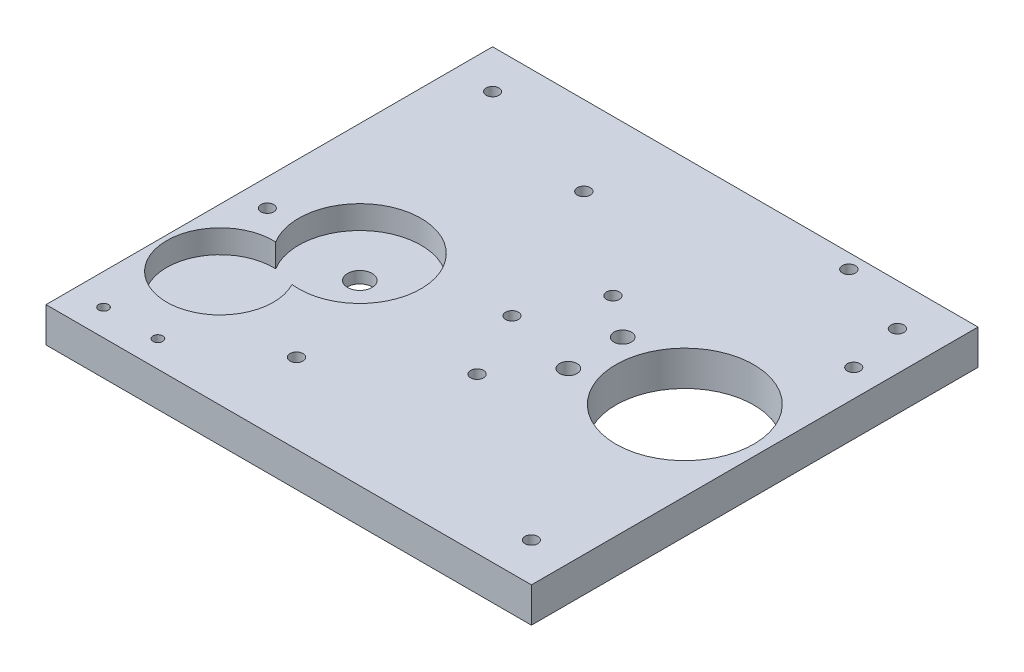
SolidWorks part; units mm, degrees
ref_plane "Front" through (0, 0, 0) normal (0, 0, 1) x (1, 0, 0)
ref_plane "Top" through (0, 0, 0) normal (0, 1, 0) x (1, 0, 0)
ref_plane "Right" through (0, 0, 0) normal (1, 0, 0) x (0, 0, -1)
sketch "Sketch1" plane through (0, 0, 0) normal (0, 1, 0) x (1, 0, 0)
  line L1 (0, 0) -> (125, 0)
  line L2 (0, 0) -> (0, 115)
  line L3 (0, 115) -> (125, 115)
  line L4 (125, 0) -> (125, 115)
  dimension "D1" = 125
  dimension "D2" = 115
extrude "Top_Base" add sketch "Sketch1" along normal blind 9
sketch "Fingers_Position" plane through (0, 9, 0) normal (0, 1, 0) x (1, 0, 0)
  line L0 (74.5, 94.5) -> (39.5, 94.5) construction
  line L1 (74.5, 78.5) -> (19.5, 78.5) construction
  line L2 (74.5, 78.5) -> (74.5, 110.5) construction
  line L3 (74.5, 110.5) -> (19.5, 110.5) construction
  line L4 (19.5, 78.5) -> (19.5, 110.5) construction
  line L5 (74.5, 9.5) -> (19.5, 9.5) construction
  line L6 (74.5, 9.5) -> (74.5, 41.5) construction
  line L7 (74.5, 41.5) -> (19.5, 41.5) construction
  line L8 (19.5, 9.5) -> (19.5, 41.5) construction
  line L10 (39.5, 25.5) -> (74.5, 25.5) construction
  line L11 (125, 115) -> (0, 115) construction
  line L12 (0, 115) -> (0, 0) construction
  dimension "D1" = 55
  dimension "D2" = 32
  dimension "D3" = 69
  dimension "D4" = 4.5
  dimension "D5" = 19.5
  dimension "D6" = 20
sketch "Intermediate_Gear_Position" plane through (0, 9, 0) normal (0, 1, 0) x (1, 0, 0)
  line L0 (0, 51.7935) -> (29.0154, 51.7935) construction
  line L1 (0, 115) -> (0, 0) construction
  line L2 (29.0154, 51.7935) -> (29.0154, 115) construction
  line L3 (125, 115) -> (0, 115) construction
  line L4 (29.0154, 51.7935) -> (29.0154, 0) construction
  line L5 (0, 0) -> (125, 0) construction
  circle A0 centre (29.0154, 51.7935) radius 15.5 construction
  circle A1 centre (29.0154, 51.7935) radius 13.5625
  circle A2 centre (29.0154, 51.7935) radius 13.8125 construction
  dimension "D3" = 31
  dimension "D4" = 27.125
  dimension "D5" = 27.625
  dimension "D1" = 29.0154
  dimension "D2" = 51.7935
sketch "Drive_Gear_Position" plane through (0, 9, 0) normal (0, 1, 0) x (1, 0, 0)
  line L0 (3, 20.8203) -> (27, 20.8203) construction
  line L1 (3, 38.8203) -> (27, 38.8203)
  line L2 (3, 38.8203) -> (3, 2.8203)
  line L3 (3, 2.8203) -> (27, 2.8203)
  line L4 (27, 38.8203) -> (27, 2.8203)
  line L5 (15, 38.8203) -> (15, 2.8203) construction
  line L6 (95.5, 103) -> (95.5, 48) construction
  line L7 (79.5, 103) -> (111.5, 103) construction
  line L8 (79.5, 103) -> (79.5, 48) construction
  line L9 (79.5, 48) -> (111.5, 48) construction
  line L10 (111.5, 103) -> (111.5, 48) construction
  line L11 (77.5, 72) -> (113.5, 72) construction
  line L12 (77.5, 72) -> (77.5, 48) construction
  line L13 (77.5, 48) -> (113.5, 48) construction
  line L14 (113.5, 72) -> (113.5, 48) construction
  line L15 (95.5, 72) -> (95.5, 48) construction
  line L17 (125, 0) -> (125, 115) construction
  line L18 (125, 115) -> (0, 115) construction
  line L20 (0, 115) -> (0, 0) construction
  circle A0 centre (15, 29.8203) radius 9 construction
  circle A1 centre (15, 29.8203) radius 13.5 construction
  circle A2 centre (15, 29.8203) radius 12
  circle A4 centre (15, 29.8203) radius 12.25 construction
  circle A5 centre (29.0154, 51.7935) radius 13.8125 construction
  dimension "D1" = 27
  dimension "D2" = 18
  dimension "D5" = 24
  dimension "D13" = 24.5
  dimension "D3" = 24
  dimension "D4" = 36
  dimension "D6" = 32
  dimension "D7" = 55
  dimension "D8" = 24
  dimension "D9" = 36
  dimension "D10" = 13.5
  dimension "D11" = 12
  dimension "D12" = 3
sketch "Sketch5" plane through (0, 9, 0) normal (0, 1, 0) x (1, 0, 0)
  circle A0 centre (29.0154, 51.7935) radius 15.75
  circle A1 centre (15, 29.8203) radius 13.75
  dimension "D1" = 27.5
  dimension "D2" = 31.5
extrude "Gears_Extrude_Cut" cut sketch "Sketch5" against normal blind 6 contours A0 A1 | A1 A0 | A0 A1 region at (29.3388, 9, -52.3005) region at (21.457, 9, -39.9435) region at (14.6326, 9, -29.2443)
sketch "Sketch7" plane through (0, 9, 0) normal (0, 1, 0) x (1, 0, 0)
  circle A0 centre (29.0154, 51.7935) radius 3.15
  dimension "D1" = 6.3
extrude "Key_Extrude_Cut" cut sketch "Sketch7" against normal through all
sketch "Sketch8" plane through (0, 9, 0) normal (0, 1, 0) x (1, 0, 0)
  line L0 (113.5, 60) -> (77.5, 60) construction
  line L1 (113.5, 72) -> (113.5, 48) construction
  line L2 (77.5, 72) -> (77.5, 48) construction
  circle A0 centre (104.5, 60) radius 9 construction
  circle A1 centre (104.5, 60) radius 17.75
  dimension "D1" = 18
  dimension "D2" = 35.5
extrude "Thumb_Extrude_Cut" cut sketch "Sketch8" against normal through all
sketch "Sketch9" plane through (0, 9, 0) normal (0, 1, 0) x (1, 0, 0)
  line L0 (74.5, 78.5) -> (19.5, 78.5) construction
  line L1 (74.5, 71.5) -> (67.5, 71.5) construction
  line L2 (74.5, 71.5) -> (74.5, 78.5) construction
  line L3 (74.5, 78.5) -> (67.5, 78.5) construction
  line L4 (67.5, 71.5) -> (67.5, 78.5) construction
  line L5 (74.5, 71.5) -> (67.5, 78.5) construction
  line L6 (74.5, 78.5) -> (67.5, 71.5) construction
  line L11 (125, 57.5) -> (0, 57.5) construction
  line L12 (125, 0) -> (125, 115) construction
  line L14 (74.5, 78.5) -> (74.5, 110.5) construction
  line L16 (0, 115) -> (0, 0) construction
  line L17 (74.5, 110.5) -> (19.5, 110.5) construction
  line L18 (74.5, 78.5) -> (47.5, 78.5) construction
  line L19 (74.5, 78.5) -> (74.5, 110.5) construction
  line L20 (74.5, 110.5) -> (47.5, 110.5) construction
  line L21 (47.5, 78.5) -> (47.5, 110.5) construction
  line L26 (74.5, 94.5) -> (39.5, 94.5) construction
  line L27 (40.5, 98) -> (47.5, 98) construction
  line L28 (40.5, 98) -> (40.5, 91) construction
  line L29 (40.5, 91) -> (47.5, 91) construction
  line L30 (47.5, 98) -> (47.5, 91) construction
  line L31 (40.5, 98) -> (47.5, 91) construction
  line L32 (40.5, 91) -> (47.5, 98) construction
  line L33 (27, 2.8203) -> (27, 0.8203) construction
  line L34 (27, 0.8203) -> (22, 0.8203) construction
  line L35 (22, 0.8203) -> (22, 6.8203) construction
  line L36 (77.5, 60) -> (113.5, 60) construction
  line L37 (77.5, 72) -> (77.5, 48) construction
  line L38 (113.5, 72) -> (113.5, 48) construction
  line L39 (77.5, 72) -> (75.5, 72) construction
  line L40 (75.5, 72) -> (75.5, 67) construction
  line L41 (75.5, 67) -> (81.5, 67) construction
  line L42 (111.5, 103) -> (111.5, 107.75) construction
  line L43 (111.5, 107.75) -> (95.5, 107.75) construction
  line L44 (111.5, 107.75) -> (115, 107.75) construction
  line L45 (115, 107.75) -> (115, 104.25) construction
  line L46 (95.5, 107.75) -> (95.5, 111.25) construction
  line L47 (15, 2.8203) -> (15, 38.8203) construction
  circle A0 centre (71, 75) radius 1.675
  circle A2 centre (44, 94.5) radius 1.675
  circle A3 centre (22, 6.8203) radius 2.25 construction
  circle A4 centre (81.5, 67) radius 2.25
  circle A5 centre (95.5, 111.25) radius 1.675
  circle A6 centre (115, 104.25) radius 1.675
  circle A7 centre (71, 40) radius 1.675
  circle A8 centre (44, 20.5) radius 1.675
  circle A9 centre (8, 6.8203) radius 2.25 construction
  circle A10 centre (81.5, 53) radius 2.25
  point P0 (71, 75)
  point P18 (44, 94.5)
  dimension "D3" = 3.35
  dimension "D10" = 4.5
  dimension "D14" = 4.5
  dimension "D1" = 7
  dimension "D2" = 7
  dimension "D4" = 27
  dimension "D5" = 7
  dimension "D6" = 7
  dimension "D7" = 2
  dimension "D8" = 5
  dimension "D9" = 6
  dimension "D11" = 2
  dimension "D12" = 5
  dimension "D13" = 6
  dimension "D15" = 4.75
  dimension "D16" = 16
  dimension "D17" = 3.5
  dimension "D18" = 3.5
  dimension "D19" = 3.5
extrude "Mount_Holes" cut sketch "Sketch9" against normal blind 5
sketch "Sketch11" plane through (0, 9, 0) normal (0, 1, 0) x (1, 0, 0)
  line L0 (0, 115) -> (10, 115) construction
  line L1 (125, 115) -> (0, 115) construction
  line L2 (10, 115) -> (10, 105) construction
  line L3 (125, 0) -> (115, 0) construction
  line L4 (0, 0) -> (125, 0) construction
  line L5 (115, 0) -> (115, 10) construction
  line L6 (0, 57.5) -> (125, 57.5) construction
  line L7 (0, 115) -> (0, 0) construction
  line L8 (125, 0) -> (125, 115) construction
  line L9 (62.5, 115) -> (62.5, 0) construction
  line L10 (125, 115) -> (125, 90) construction
  line L11 (125, 90) -> (118, 90) construction
  line L12 (0, 0) -> (0, 50) construction
  line L13 (0, 50) -> (7, 50) construction
  circle A0 centre (10, 105) radius 2.8
  circle A1 centre (115, 10) radius 2.8
  circle A2 centre (62.5, 57.5) radius 2.8
  circle A3 centre (118, 90) radius 2.8
  circle A4 centre (7, 50) radius 2.8
  dimension "D5" = 5.6
  dimension "D1" = 10
  dimension "D2" = 10
  dimension "D3" = 10
  dimension "D4" = 10
  dimension "D6" = 25
  dimension "D7" = 7
  dimension "D8" = 50
  dimension "D9" = 7
hole_wizard "M3x0.5 Tapped Hole1" positions "3DSketch1" profile "Sketch14" tap size "M3x0.5" standard "ANSI Metric"
sketch3d "3DSketch1"
  point P0 (8, 9, -6.8203)
  point P3 (22, 9, -6.8203)
sketch "Sketch14" plane through (8, 9, -6.8203) normal (1, 0, 0) x (0, 0, 1)
  line L0 (0, 0) -> (0, 8.2511)
  line L1 (0, 8.2511) -> (1.25, 7.5)
  line L2 (1.25, 7.5) -> (1.25, 0)
  line L5 (1.25, 0) -> (0, 0)
  line L10 (0, 8.2511) -> (-1.25, 7.5) construction
  line L11 (0, -6.35) -> (0, 107.95) construction
  dimension "Tap Drill Dia." = 2.5
  dimension "Tap Drill Depth" = 7.5
  dimension "Drill Angle" = 118
cosmetic thread "Hole Thread1" parameters "D1"=6, "D2"=3
cosmetic thread "Hole Thread2" parameters "D1"=6, "D2"=3
hole_wizard "M4x0.7 Tapped Hole1" positions "3DSketch3" profile "Sketch16" tap size "M4x0.7" standard "ANSI Metric"
sketch3d "3DSketch3"
  point P0 (10, 9, -105)
  point P3 (118, 9, -90)
  point P6 (115, 9, -10)
  point P9 (7, 9, -50)
  point P12 (62.5, 9, -57.5)
sketch "Sketch16" plane through (10, 9, -105) normal (1, 0, 0) x (0, 0, 1)
  line L0 (0, 0) -> (0, 11.0914)
  line L1 (0, 11.0914) -> (1.65, 10.1)
  line L2 (1.65, 10.1) -> (1.65, 0)
  line L5 (1.65, 0) -> (0, 0)
  line L10 (0, 11.0914) -> (-1.65, 10.1) construction
  line L11 (0, -6.35) -> (0, 107.95) construction
  dimension "Tap Drill Dia." = 3.3
  dimension "Tap Drill Depth" = 10.1
  dimension "Drill Angle" = 118
cosmetic thread "Hole Thread3" parameters "D1"=8, "D2"=4
cosmetic thread "Hole Thread4" parameters "D1"=8, "D2"=4
cosmetic thread "Hole Thread5" parameters "D1"=8, "D2"=4
cosmetic thread "Hole Thread6" parameters "D1"=8, "D2"=4
cosmetic thread "Hole Thread7" parameters "D1"=8, "D2"=4
